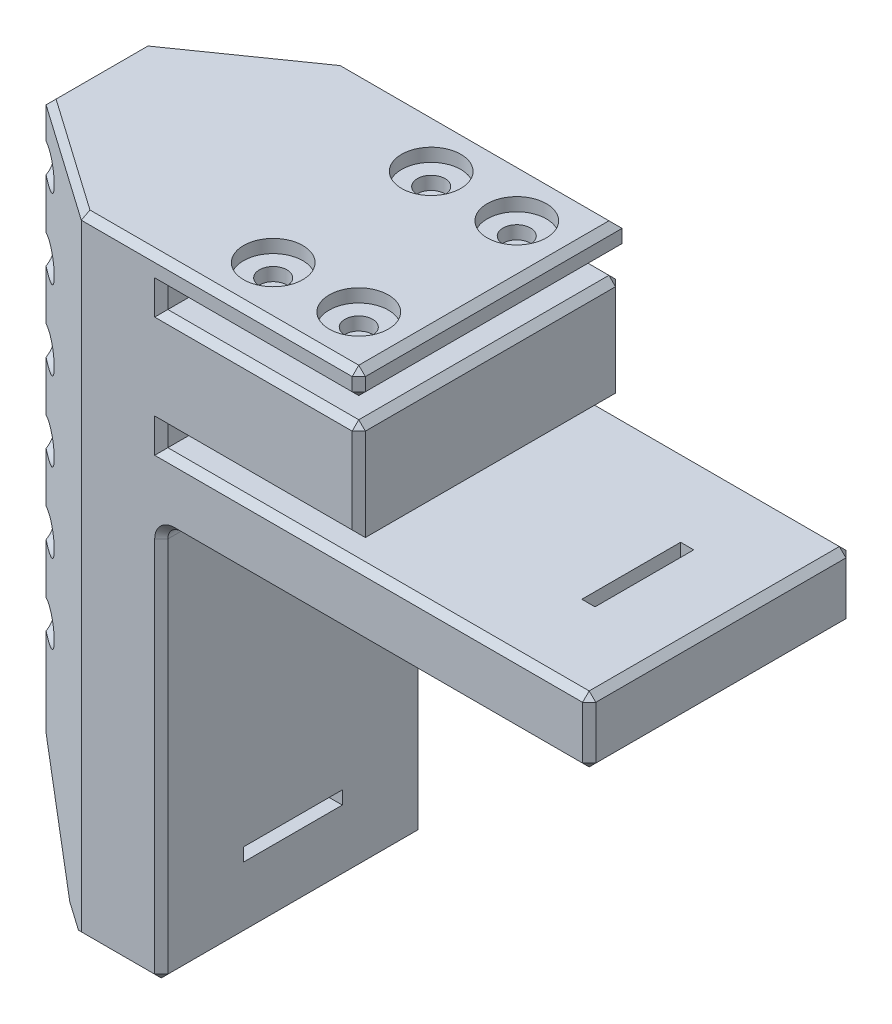
SolidWorks part; units mm, degrees
ref_plane "Front Plane" through (0, 0, 0) normal (0, 0, 1) x (1, 0, 0)
ref_plane "Top Plane" through (0, 0, 0) normal (0, 1, 0) x (1, 0, 0)
ref_plane "Right Plane" through (0, 0, 0) normal (1, 0, 0) x (0, 0, -1)
sketch "Sketch1" plane through (0, 0, 0) normal (0, 0, 1) x (1, 0, 0)
  line L0 (-15, 10.675) -> (15, 10.675)
  line L1 (-15, -7.5) -> (15, -7.5)
  line L3 (-15, 7.5) -> (15, 7.5)
  line L4 (15, -7.5) -> (15, 7.5)
  line L5 (-15, -7.5) -> (15, 7.5) construction
  line L6 (-15, 7.5) -> (15, -7.5) construction
  line L7 (15, 10.675) -> (15, 14.675)
  line L8 (15, 14.675) -> (-45, 14.675)
  line L9 (-45, 14.675) -> (-45, -80.9389)
  line L10 (-45, -80.9389) -> (-15, -80.9389)
  line L11 (-15, -80.9389) -> (-15, -22.675)
  line L12 (-13, -20.675) -> (50, -20.675)
  line L13 (50, -20.675) -> (50, -10.675)
  line L14 (50, -10.675) -> (-15, -10.675)
  line L15 (-15, -10.675) -> (-15, -7.5)
  line L16 (-15, 7.5) -> (-15, 10.675)
  arc A1 (-13, -20.675) -> (-15, -22.675) centre (-13, -22.675) ccw
  point P0 (0, 0)
  dimension "D6" = 2
  dimension "D7" = 65
  dimension "D1" = 4
  dimension "D2" = 3.175
  dimension "D3" = 15
  dimension "D4" = 30
  dimension "D5" = 30
  dimension "D8" = 10
extrude "Boss-Extrude1" add sketch "Sketch1" along normal blind 40
ref_plane "Plane1" through (0, 6.675, 0) normal (0, 1, 0) x (1, 0, 0)
sketch "Sketch2" plane through (0, 6.675, 0) normal (0, 1, 0) x (1, 0, 0)
  line L0 (-45, -20) -> (15, -20) construction
  line L1 (-45, -40) -> (-45, 0) construction
  line L2 (15, -40) -> (15, 0) construction
  circle A0 centre (-45, -20) radius 8.7
  dimension "D1" = 17.4
sketch "Sketch3" plane through (0, 14.675, 0) normal (0, 1, 0) x (1, 0, 0)
  line L0 (-43.3548, -40) -> (-45, -38.9316)
  line L1 (15, -40) -> (-45, -40) construction
  line L2 (-45, -40) -> (-45, 0) construction
  line L3 (-45, -38.9316) -> (-45, -40)
  line L4 (-45, -40) -> (-43.3548, -40)
  line L6 (-45, -20) -> (-51.6989, -20) construction
  line L7 (-45, 0) -> (-43.3548, 0)
  line L8 (-45, -1.0684) -> (-45, 0)
  line L9 (-43.3548, 0) -> (-45, -1.0684)
  dimension "D2" = 33
extrude "Cut-Extrude1" cut sketch "Sketch3" against normal blind 182
sweep "Cut-Sweep1" cut path "Sketch2" circular profile diameter 5 parameters "D3"=5
pattern_linear "LPattern1" count 6 spacing 12 along (0, -1, 0) of "Cut-Sweep1"
sketch "Sketch51" plane through (0, 14.675, 0) normal (0, 1, 0) x (1, 0, 0)
  line L0 (-27.1481, -40) -> (-45, -27.5)
  line L1 (-45, -38.9316) -> (-45, -1.0684) construction
  line L2 (-45, -27.5) -> (-45, -12.5)
  line L3 (-45, -12.5) -> (-27.1481, 0)
  line L4 (-27.1481, 0) -> (-27.1481, -45.5737)
  line L5 (15, -20) -> (-45, -20) construction
  line L6 (15, -40) -> (15, 0) construction
  line L7 (15, -40) -> (-43.3548, -40) construction
  line L8 (15, 0) -> (-43.3548, 0) construction
  line M6 (-45, -1.0684) -> (-45, -38.9316)
  line M7 (-45, -38.9316) -> (-43.3548, -40)
  line M8 (-43.3548, -40) -> (15, -40)
  line M10 (15, 0) -> (-43.3548, 0)
  line M11 (-43.3548, 0) -> (-45, -1.0684)
  dimension "D1" = 35
  dimension "D2" = 15
extrude "Cut-Extrude6" cut sketch "Sketch51" against normal blind 105 contours L3 M6 M10 M11 | L0 M8 M6 M7 region at (-39.0065, 14.675, 35.8031) region at (-39.0065, 14.675, 4.1969)
chamfer "Chamfer1" distance 1 angle 45 37 edges at (-45, 14.675, 20) (-6.0741, 14.675, 0) (17.5, -10.675, 0) (-15, -9.0875, 0) (0, -7.5, 0) (15, 14.675, 20) (15, 10.675, 20) (0, 10.675, 0) (-15, 9.0875, 0) (0, 7.5, 0) (15, 0, 0) (50, -15.675, 0) (50, -10.675, 20) (15, 7.5, 20) (-6.0741, 14.675, 40) (15, 12.675, 40) (0, 10.675, 40) (-15, 9.0875, 40) (0, 7.5, 40) (15, 0, 40) (0, -7.5, 40) (-15, -9.0875, 40) (17.5, -10.675, 40) (50, -15.675, 40) (-45, -80.9389, 20) (-21.0741, -80.9389, 0) (-15, -80.9389, 20) (-21.0741, -80.9389, 40) (-15, -51.8069, 40) (18.5, -20.675, 40) (-15, -51.8069, 0) (-14.4142, -21.2608, 0) (18.5, -20.675, 0) (-14.4142, -21.2608, 40) (-36.0741, 14.675, 6.25) (-36.0741, 14.675, 33.75) (50, -20.675, 20)
sketch "Sketch32" plane through (0, -7.5, 0) normal (0, -1, 0) x (1, 0, 0)
  line L0 (50, 20) -> (-15, 20) construction
  line L1 (-6, 32) -> (7, 32) construction
  line L2 (-6, 32) -> (-6, 8) construction
  line L3 (-6, 8) -> (7, 8) construction
  line L4 (7, 32) -> (7, 8) construction
  line L5 (50, 39) -> (50, 1) construction
  line L7 (15, 39) -> (15, 0) construction
  line L8 (-16, 1) -> (-16, 39) construction
  line L9 (-13, 40) -> (49, 40) construction
  line L10 (-15, 39) -> (-15, 1) construction
  circle A0 centre (7, 32) radius 2.1
  circle A1 centre (-6, 32) radius 2.1
  circle A2 centre (-6, 8) radius 2.1
  circle A3 centre (7, 8) radius 2.1
  point P10 (-6, 20)
  dimension "D4" = 4.2
  dimension "D3" = 10
  dimension "D2" = 8
  dimension "D1" = 8
extrude "Cut-Extrude2" cut sketch "Sketch32" against normal blind 10 from surface starting at face at (-0.5, 10.675, 20)
sketch "Sketch34" plane through (0, 7.5, 0) normal (0, 1, 0) x (1, 0, 0)
  circle A0 centre (-6, -32) radius 2.1
  circle A1 centre (7, -32) radius 2.1
  circle A2 centre (7, -8) radius 2.1
  circle A3 centre (-6, -8) radius 2.1
  dimension "D1" = 4.2
extrude "Cut-Extrude3" cut sketch "Sketch34" against normal blind 51
sketch "Sketch60" plane through (-15, 0, 0) normal (1, 0, 0) x (0, 0, -1)
  line L0 (-27.5, -69.9389) -> (-40, -69.9389) construction
  line L1 (-27.5, -68.9389) -> (-12.5, -68.9389)
  line L2 (-27.5, -68.9389) -> (-27.5, -70.9389)
  line L3 (-27.5, -70.9389) -> (-12.5, -70.9389)
  line L4 (-12.5, -68.9389) -> (-12.5, -70.9389)
  line L5 (-40, -79.9389) -> (-40, -22.675) construction
  line L6 (-12.5, -69.9389) -> (0, -69.9389) construction
  line L7 (0, -22.675) -> (0, -79.9389) construction
  line L8 (-1, -80.9389) -> (-39, -80.9389) construction
  dimension "D1" = 12
  dimension "D2" = 2
  dimension "D3" = 15
extrude "Cut-Extrude7" cut sketch "Sketch60" against normal blind 42
sketch "Sketch76" plane through (0, 0, 40) normal (0, 0, 1) x (1, 0, 0)
  line L0 (-45, -68.9389) -> (-26.3889, -87.5499)
  line L1 (-26.3889, -87.5499) -> (-45, -87.5499)
  line L6 (-45, -68.9389) -> (-45, -55.5182) construction
  line L7 (-45, -68.9389) -> (-45, -87.5499)
  point P4 (-41.4296, -68.9389)
  point P5 (-44.7667, -84.9425)
  point P6 (-45, -65.5097)
  point P7 (-45, -68.9389)
  point P9 (0, 0)
  point P10 (0, 0)
  point P13 (0, 0)
  point P14 (-44.8465, -65.6632)
  dimension "D1" = 45
extrude "Cut-Extrude10" cut sketch "Sketch76" against normal blind 121
sketch "Sketch77" plane through (0, -20.675, 0) normal (0, -1, 0) x (1, 0, 0)
  line L0 (23.7567, 27.5) -> (23.7567, 40) construction
  line L1 (36.3832, 27.5) -> (38.3832, 27.5)
  line L2 (36.3832, 27.5) -> (36.3832, 12.5)
  line L3 (36.3832, 12.5) -> (38.3832, 12.5)
  line L4 (38.3832, 27.5) -> (38.3832, 12.5)
  line L5 (-13, 40) -> (49, 40) construction
  line L6 (23.7567, 12.5) -> (23.7567, 0) construction
  line L7 (49, 0) -> (-13, 0) construction
  dimension "D1" = 15
  dimension "D2" = 2
extrude "Cut-Extrude11" cut sketch "Sketch77" against normal blind 121
sketch "Sketch78" plane through (0, -20.675, 0) normal (0, -1, 0) x (1, 0, 0)
  line L1 (-1.2617, 32) -> (-3.6308, 36.1035)
  line L2 (-3.6308, 36.1035) -> (-8.3692, 36.1035)
  line L3 (-8.3692, 36.1035) -> (-10.7383, 32)
  line L4 (-10.7383, 32) -> (-8.3692, 27.8965)
  line L5 (-8.3692, 27.8965) -> (-3.6308, 27.8965)
  line L6 (-3.6308, 27.8965) -> (-1.2617, 32)
  line L7 (11.7383, 32) -> (9.3692, 36.1035)
  line L8 (9.3692, 36.1035) -> (4.6308, 36.1035)
  line L9 (4.6308, 36.1035) -> (2.2617, 32)
  line L10 (2.2617, 32) -> (4.6308, 27.8965)
  line L11 (4.6308, 27.8965) -> (9.3692, 27.8965)
  line L12 (9.3692, 27.8965) -> (11.7383, 32)
  line L13 (11.7383, 8) -> (9.3692, 12.1035)
  line L14 (9.3692, 12.1035) -> (4.6308, 12.1035)
  line L15 (4.6308, 12.1035) -> (2.2617, 8)
  line L16 (2.2617, 8) -> (4.6308, 3.8965)
  line L17 (4.6308, 3.8965) -> (9.3692, 3.8965)
  line L18 (9.3692, 3.8965) -> (11.7383, 8)
  line L19 (-1.2617, 8) -> (-3.6308, 12.1035)
  line L20 (-3.6308, 12.1035) -> (-8.3692, 12.1035)
  line L21 (-8.3692, 12.1035) -> (-10.7383, 8)
  line L22 (-10.7383, 8) -> (-8.3692, 3.8965)
  line L23 (-8.3692, 3.8965) -> (-3.6308, 3.8965)
  line L24 (-3.6308, 3.8965) -> (-1.2617, 8)
  circle A0 centre (-6, 32) radius 4.1035 construction
  circle A1 centre (7, 32) radius 4.1035 construction
  circle A2 centre (7, 8) radius 4.1035 construction
  circle A3 centre (-6, 8) radius 4.1035 construction
  point P28 (-9.9523, 8)
  point P37 (-1.2617, 8)
extrude "Cut-Extrude12" cut sketch "Sketch78" against normal blind 5
sketch "Sketch79" plane through (0, 14.675, 0) normal (0, 1, 0) x (1, 0, 0)
  circle A0 centre (-6, -8) radius 4.5
  circle A1 centre (7, -8) radius 4.5
  circle A2 centre (7, -32) radius 4.5
  circle A3 centre (-6, -32) radius 4.5
  point P11 (7, -32)
  dimension "D1" = 9
extrude "Cut-Extrude13" cut sketch "Sketch79" against normal blind 2
equation "\"D3@Sketch32\"=10"
equation "\"D2@Sketch32\"=\"D1@Sketch32\""
